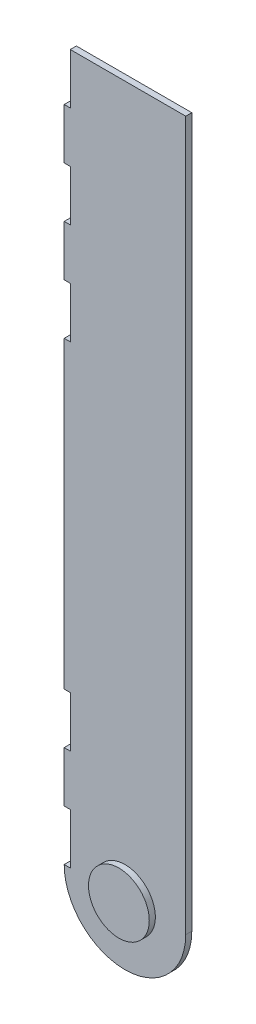
SolidWorks part; units mm, degrees
ref_plane "Plan de face" through (0, 0, 0) normal (0, 0, 1) x (1, 0, 0)
ref_plane "Plan de dessus" through (0, 0, 0) normal (0, 1, 0) x (1, 0, 0)
ref_plane "Plan de droite" through (0, 0, 0) normal (1, 0, 0) x (0, 0, -1)
sketch "Esquisse1" plane through (0, 0, 0) normal (0, 0, 1) x (1, 0, 0)
  line L1 (0, 0) -> (60, 0)
  line L2 (0, 0) -> (0, 380)
  line L3 (0, 380) -> (60, 380)
  line L4 (60, 0) -> (60, 380)
  dimension "D1" = 60
  dimension "D2" = 380
extrude "Boss.-Extru.1" add sketch "Esquisse1" along normal blind 3
fillet "Congé1" radius 30 2 edges at (0, 0, 1.5) (60, 0, 1.5)
sketch "Esquisse2" plane through (0, 0, 3) normal (0, 0, 1) x (1, 0, 0)
  line L0 (0, 380) -> (0, 30) construction
  line L1 (0, 380) -> (3, 380)
  line L2 (0, 380) -> (0, 355)
  line L3 (0, 355) -> (3, 355)
  line L4 (3, 380) -> (3, 355)
  line L5 (0, 330) -> (3, 330)
  line L6 (0, 330) -> (0, 305)
  line L7 (0, 305) -> (3, 305)
  line L8 (3, 330) -> (3, 305)
  line L9 (60, 380) -> (0, 380) construction
  line L11 (0, 280) -> (3, 280)
  line L12 (0, 280) -> (0, 255)
  line L13 (0, 255) -> (3, 255)
  line L14 (3, 280) -> (3, 255)
  point P13 (1.5, 355)
  dimension "D1" = 3
  dimension "D2" = 3
  dimension "D3" = 25
  dimension "D4" = 25
  dimension "D5" = 25
  dimension "D6" = 3
  dimension "D7" = 25
  dimension "D8" = 25
extrude "Enlèv. mat.-Extru.1" cut sketch "Esquisse2" against normal blind 3
sketch "Esquisse3" plane through (0, 0, 3) normal (0, 0, 1) x (1, 0, 0)
  line L0 (60, 30) -> (60, 380) construction
  circle A0 centre (30, 30) radius 15
  dimension "D1" = 30
  dimension "D2" = 30
  dimension "D3" = 30
extrude "Boss.-Extru.2" add sketch "Esquisse3" along normal blind 3
sketch "Esquisse4" plane through (0, 0, 3) normal (0, 0, 1) x (1, 0, 0)
  line L0 (0, 255) -> (0, 30) construction
  line L1 (0, 30) -> (3, 30)
  line L2 (0, 30) -> (0, 55)
  line L3 (0, 55) -> (3, 55)
  line L4 (3, 30) -> (3, 55)
  line L5 (0, 80) -> (3, 80)
  line L6 (0, 80) -> (0, 105)
  line L7 (0, 105) -> (3, 105)
  line L8 (3, 80) -> (3, 105)
  dimension "D1" = 3
  dimension "D2" = 3
  dimension "D3" = 25
  dimension "D4" = 25
  dimension "D5" = 25
extrude "Enlèv. mat.-Extru.2" cut sketch "Esquisse4" against normal blind 3
